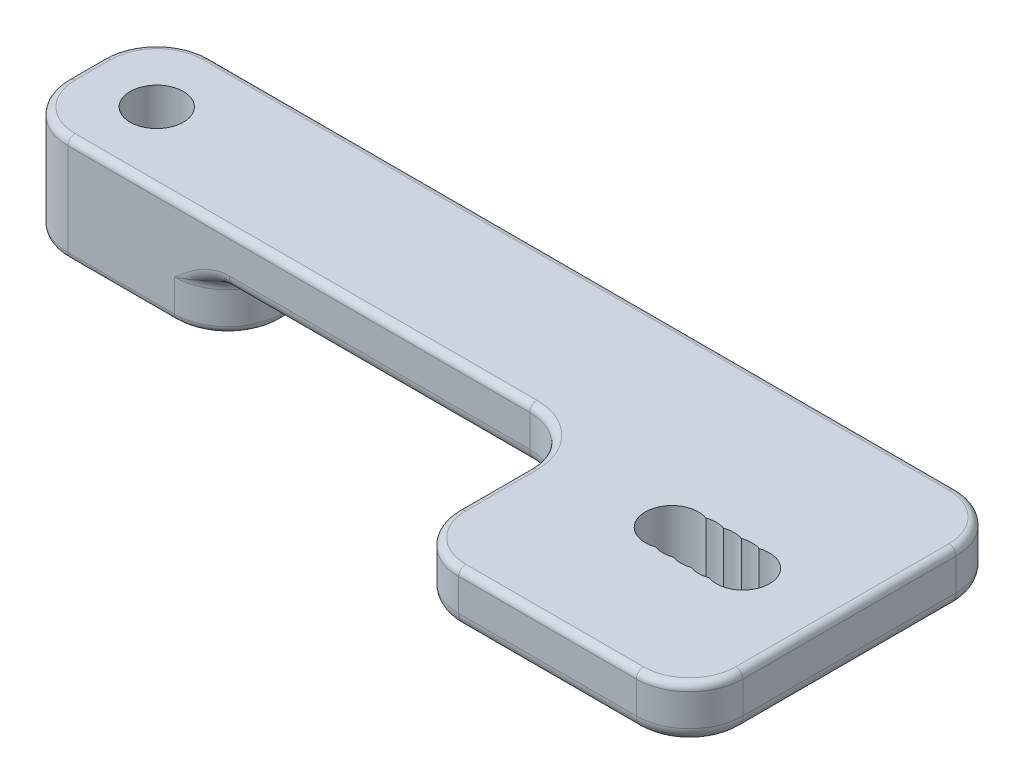
SolidWorks part; units mm, degrees
ref_plane "Front Plane" through (0, 0, 0) normal (0, 0, 1) x (1, 0, 0)
ref_plane "Top Plane" through (0, 0, 0) normal (0, 1, 0) x (1, 0, 0)
ref_plane "Right Plane" through (0, 0, 0) normal (1, 0, 0) x (0, 0, -1)
sketch "Sketch1" plane through (0, 0, 0) normal (0, 1, 0) x (1, 0, 0)
  line L1 (0, 0) -> (48, 0)
  line L2 (0, 0) -> (0, -8)
  line L3 (0, -8) -> (48, -8)
  line L4 (48, 0) -> (48, -8)
  dimension "D1" = 8
  dimension "D2" = 48
extrude "Boss-Extrude1" add sketch "Sketch1" along normal blind 3
sketch "Sketch3" plane through (0, 0, 0) normal (0, -1, 0) x (-1, 0, 0)
  line L0 (0, -8) -> (-48, -8) construction
  line L1 (0, 0) -> (-12, 0)
  line L2 (0, 0) -> (0, -8)
  line L3 (0, -8) -> (-12, -8)
  line L4 (-12, 0) -> (-12, -8)
  dimension "D1" = 12
extrude "Boss-Extrude2" add sketch "Sketch3" along normal blind 3
sketch "Sketch2" plane through (0, 3, 0) normal (0, 1, 0) x (1, 0, 0)
  line L0 (0, 0) -> (0, -8) construction
  line L1 (0, -8) -> (48, -8) construction
  circle A0 centre (4, -4) radius 1.5
  dimension "D2" = 3
  dimension "D4" = 4
  dimension "D5" = 4
extrude "Cut-Extrude1" cut sketch "Sketch2" against normal through all
sketch "Sketch4" plane through (0, 0, 8) normal (0, 0, 1) x (1, 0, 0)
  line L0 (12, 0) -> (48, 0) construction
  line L1 (48, 3) -> (32, 3)
  line L2 (48, 3) -> (48, 0)
  line L3 (48, 0) -> (32, 0)
  line L4 (32, 3) -> (32, 0)
  dimension "D1" = 16
extrude "Boss-Extrude3" add sketch "Sketch4" along normal blind 10
sketch "Sketch5" plane through (0, 3, 0) normal (0, 1, 0) x (1, 0, 0)
  line L0 (48, -18) -> (48, 0) construction
  circle A0 centre (43, -10) radius 1.5
  circle A2 centre (42, -10) radius 1.5
  circle A3 centre (41, -10) radius 1.5
  circle A4 centre (40, -10) radius 1.5
  circle A5 centre (39, -10) radius 1.5
  circle A6 centre (4, -4) radius 1.5 construction
  dimension "D2" = 3
  dimension "D1" = 6
  dimension "D3" = 5
  dimension "D4" = 5
extrude "Cut-Extrude2" cut sketch "Sketch5" against normal blind 15 contours A2 A0 | A3 A0 A2 | A0 A3 | A2 | A3 | A5 | A4 region at (43.7007, 3, 10) region at (42.8006, 3, 10) region at (42, 3, 10)
sketch "Sketch7" plane through (0, 0, 0) normal (0, -1, 0) x (1, 0, 0)
  arc A8 (39.5, 12.958) -> (39.5, 7.042) centre (39, 10) ccw
  arc A9 (39.5, 7.042) -> (40.5, 7.042) centre (40, 10) ccw
  arc A10 (40.5, 7.042) -> (41.5, 7.042) centre (41, 10) ccw
  arc A11 (41.5, 7.042) -> (42.5, 7.042) centre (42, 10) ccw
  arc A12 (42.5, 7.042) -> (42.5, 12.958) centre (43, 10) ccw
  arc A13 (42.5, 12.958) -> (41.5, 12.958) centre (42, 10) ccw
  arc A14 (41.5, 12.958) -> (40.5, 12.958) centre (41, 10) ccw
  arc A15 (40.5, 12.958) -> (39.5, 12.958) centre (40, 10) ccw
  arc A16 (41.5, 11.4142) -> (40.5, 11.4142) centre (41, 10) ccw
  arc A17 (42.5, 11.4142) -> (41.5, 11.4142) centre (42, 10) ccw
  arc A18 (42.5, 8.5858) -> (42.5, 11.4142) centre (43, 10) ccw
  arc A19 (41.5, 8.5858) -> (42.5, 8.5858) centre (42, 10) ccw
  arc A20 (40.5, 8.5858) -> (41.5, 8.5858) centre (41, 10) ccw
  arc A21 (39.5, 8.5858) -> (40.5, 8.5858) centre (40, 10) ccw
  arc A22 (40.5, 11.4142) -> (39.5, 11.4142) centre (40, 10) ccw
  arc A23 (39.5, 11.4142) -> (39.5, 8.5858) centre (39, 10) ccw
  arc A24 (41.5, 11.4142) -> (40.5, 11.4142) centre (41, 10) ccw
  arc A25 (42.5, 11.4142) -> (41.5, 11.4142) centre (42, 10) ccw
  arc A26 (42.5, 8.5858) -> (42.5, 11.4142) centre (43, 10) ccw
  arc A27 (41.5, 8.5858) -> (42.5, 8.5858) centre (42, 10) ccw
  arc A28 (40.5, 8.5858) -> (41.5, 8.5858) centre (41, 10) ccw
  arc A29 (39.5, 8.5858) -> (40.5, 8.5858) centre (40, 10) ccw
  arc A30 (40.5, 11.4142) -> (39.5, 11.4142) centre (40, 10) ccw
  arc A31 (39.5, 11.4142) -> (39.5, 8.5858) centre (39, 10) ccw
  dimension "D1" = 0
  dimension "D2" = 1.5
extrude "Boss-Extrude5" add sketch "Sketch7" along normal blind 1.2
fillet "Fillet1" radius 3 6 edges at (32, 1.5, 8) (0, 0, 8) (0, 0, 0) (48, 1.5, 0) (32, 1.5, 18) (48, 1.5, 18)
fillet "Fillet2" radius 3 2 edges at (12, -1.5, 0) (12, -1.5, 8)
fillet "Fillet3" radius 0.8 20 edges at (36, 0, 10) (40, 0, 7) (41, 0, 7) (42, 0, 7) (46, 0, 10) (42, 0, 13) (41, 0, 13) (40, 0, 13) (11.1213, 0, 0.8787) (12, 0, 4) (11.1213, 0, 7.1213) (19, 0, 8) (31.1213, 0, 8.8787) (32, 0, 13) (32.8787, 0, 17.1213) (40, 0, 18) (47.1213, 0, 17.1213) (48, 0, 9) (47.1213, 0, 0.8787) (27, 0, 0)
fillet "Fillet4" radius 0.4 8 edges at (11.1213, -3, 7.1213) (12, -3, 4) (11.1213, -3, 0.8787) (6, -3, 0) (0.8787, -3, 0.8787) (0, -3, 4) (0.8787, -3, 7.1213) (6, -3, 8)
fillet "Fillet5" radius 0.4 12 edges at (47.1213, 3, 0.8787) (48, 3, 9) (47.1213, 3, 17.1213) (40, 3, 18) (32.8787, 3, 17.1213) (32, 3, 13) (31.1213, 3, 8.8787) (16, 3, 8) (0.8787, 3, 7.1213) (0, 3, 4) (0.8787, 3, 0.8787) (24, 3, 0)
sketch "Sketch8" plane through (0, -3, 0) normal (0, -1, 0) x (-1, 0, 0)
  line L0 (-9, 0) -> (-3, 0) construction
  circle A0 centre (-8, -4) radius 1.4
  circle A1 centre (-4, -4) radius 1.5 construction
  dimension "D1" = 4
  dimension "D2" = 2.8
  dimension "D3" = 4
extrude "Boss-Extrude6" add sketch "Sketch8" along normal blind 1.2
